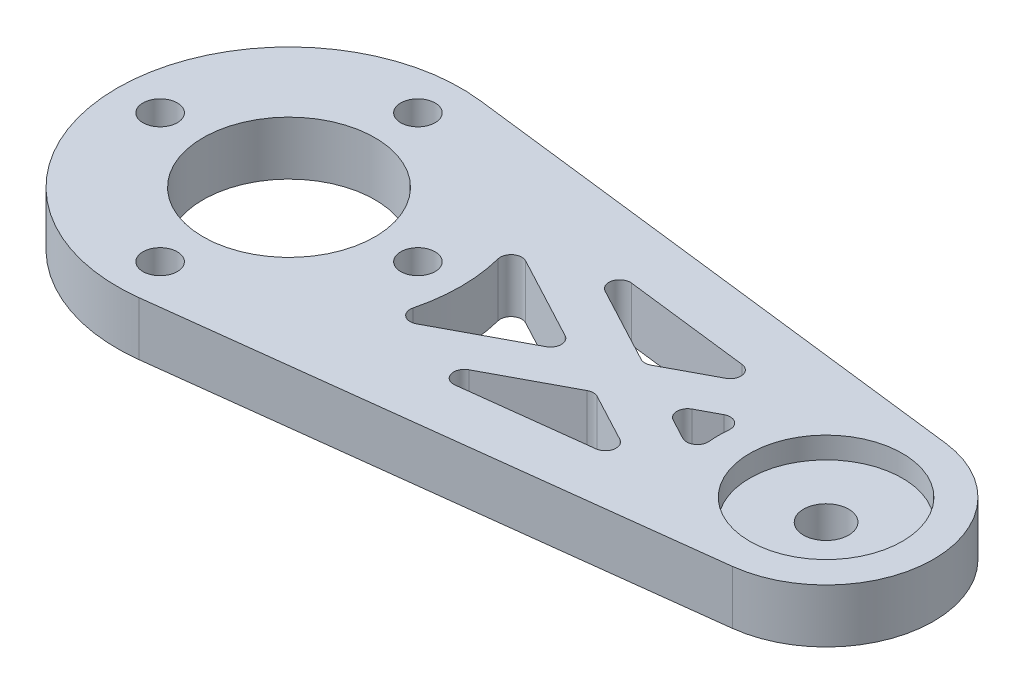
SolidWorks part; units mm, degrees
material "三聚氰胺甲醛树脂"
ref_plane "前视基准面" through (0, 0, 0) normal (0, 0, 1) x (1, 0, 0)
ref_plane "上视基准面" through (0, 0, 0) normal (0, 1, 0) x (1, 0, 0)
ref_plane "右视基准面" through (0, 0, 0) normal (1, 0, 0) x (0, 0, -1)
sketch "草图1" plane through (0, 0, 0) normal (0, 1, 0) x (1, 0, 0)
  line L0 (0, 0) -> (-5.9584, 0) construction
  line L1 (1.92, -15.8844) -> (51.2, -9.9277)
  line L2 (1.92, 15.8844) -> (51.2, 9.9277)
  line L3 (18.3565, 8.8613) -> (38.5355, 6.4222)
  line L4 (18.3565, -8.8613) -> (38.5355, -6.4222)
  line L5 (12.855, 9.5262) -> (42.0023, -6.0031) construction
  line L6 (12.855, -9.5262) -> (42.0023, 6.0031) construction
  line L7 (14.7223, 6.2652) -> (26.4816, 0)
  line L8 (18.3565, 8.8613) -> (30.735, 2.2662)
  line L9 (14.7223, -6.2652) -> (26.4816, 0)
  line L10 (18.3565, -8.8613) -> (30.735, -2.2662)
  line L11 (30.735, 2.2662) -> (38.5355, 6.4222)
  line L12 (34.9884, 0) -> (40.4294, -2.8989)
  line L13 (34.9884, 0) -> (40.4294, 2.8989)
  line L14 (30.735, -2.2662) -> (38.5355, -6.4222)
  circle A0 centre (0, 0) radius 12 construction
  circle A1 centre (-12, 0) radius 1.6
  circle A2 centre (0, 12) radius 1.6
  circle A3 centre (12, 0) radius 1.6
  circle A4 centre (0, -12) radius 1.6
  arc A5 (1.92, 15.8844) -> (1.92, -15.8844) centre (0, 0) ccw
  circle A6 centre (0, 0) radius 8
  arc A7 (40.4294, 2.8989) -> (40.4294, -2.8989) centre (50, 0) ccw
  circle A8 centre (50, 0) radius 2.1
  circle A9 centre (50, 0) radius 7.1
  arc A10 (14.7223, -6.2652) -> (14.7223, 6.2652) centre (0, 0) ccw
  circle A11 centre (0, 0) radius 16 construction
  arc A12 (51.2, -9.9277) -> (51.2, 9.9277) centre (50, 0) ccw
  circle A13 centre (50, 0) radius 10 construction
  point P15 (0, 0)
  dimension "D1" = 24
  dimension "D2" = 3.2
  dimension "D4" = 20
  dimension "D5" = 32
  dimension "D6" = 16
  dimension "D7" = 4.2
  dimension "D8" = 14.2
  dimension "D3" = 50
  dimension "D9" = 5
  dimension "D10" = 5
  dimension "D11" = 2
  dimension "D12" = 2
  dimension "D13" = 2
  dimension "D14" = 2
extrude "凸台-拉伸1" add sketch "草图1" along normal blind 5 contours L1 A7 L2 A5 A9 A1 A2 A3 A4 A6 region at (-15.1754, 0, 0)
extrude "凸台-拉伸2" add sketch "草图1<3>" along normal blind 3 contours A9 A8 region at (43.1008, 0, 0)
sketch "草图1<3>" plane through (0, 0, 0) normal (0, 1, 0) x (1, 0, 0) same geometry as "草图1"
fillet "圆角1" radius 1 3 edges at (34.9884, 2.5, 0) (40.4294, 2.5, -2.8989) (40.4294, 2.5, 2.8989)
fillet "圆角2" radius 1 3 edges at (30.735, 2.5, 2.2662) (18.3565, 2.5, 8.8613) (38.5355, 2.5, 6.4222)
fillet "圆角3" radius 1 3 edges at (18.3565, 2.5, -8.8613) (30.735, 2.5, -2.2662) (38.5355, 2.5, -6.4222)
fillet "圆角4" radius 1 3 edges at (14.7223, 2.5, -6.2652) (26.4816, 2.5, 0) (14.7223, 2.5, 6.2652)
